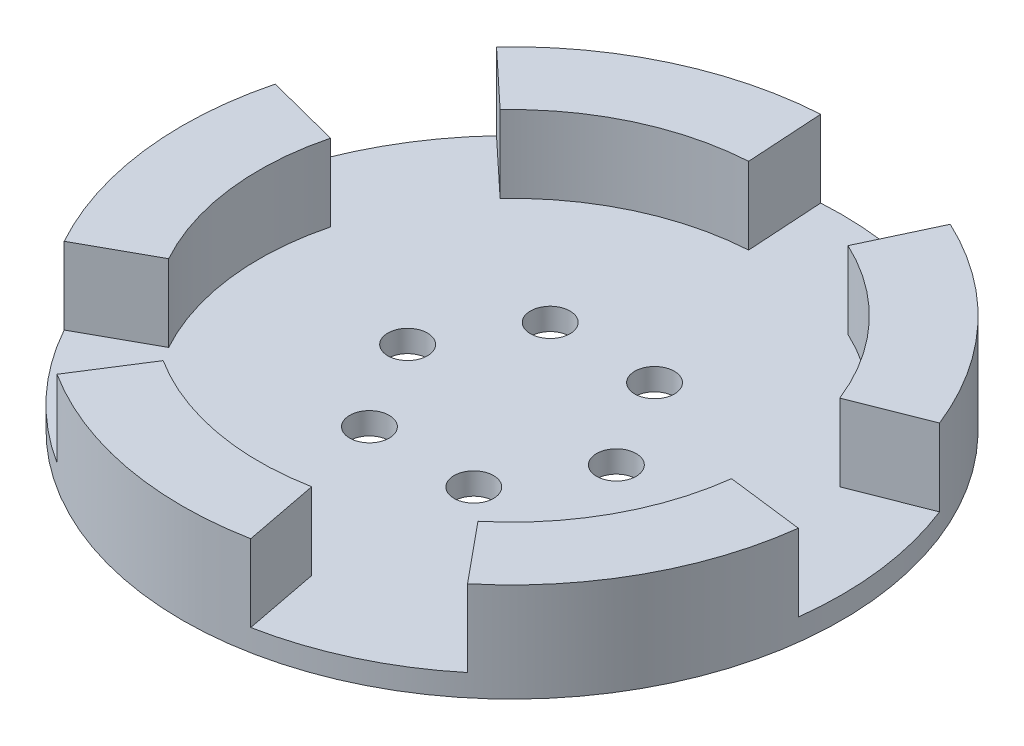
SolidWorks part; units mm, degrees
ref_plane "Front Plane" through (0, 0, 0) normal (0, 0, 1) x (1, 0, 0)
ref_plane "Top Plane" through (0, 0, 0) normal (0, 1, 0) x (1, 0, 0)
ref_plane "Right Plane" through (0, 0, 0) normal (1, 0, 0) x (0, 0, -1)
sketch "Sketch3" plane through (0, 0, 0) normal (0, 1, 0) x (1, 0, 0)
  circle A0 centre (0, 0) radius 30
  dimension "D2" = 60
extrude "Boss-Extrude3" add sketch "Sketch3" along normal blind 2
sketch "Sketch4" plane through (0, 2, 0) normal (0, 1, 0) x (1, 0, 0)
  line L0 (0, 0) -> (-16.7954, 15.7135) construction
  line L1 (0, 0) -> (9.7544, 20.8291) construction
  line L2 (0, 0) -> (21.3954, 8.4401) construction
  line L3 (0, 0) -> (22.8239, -2.8404) construction
  line L4 (0, 0) -> (14.6386, -17.7401) construction
  line L5 (0, 0) -> (4.3516, -22.5846) construction
  line L6 (0, 0) -> (-12.3483, -19.4041) construction
  line L7 (0, 0) -> (-20.1345, -11.1176) construction
  line L8 (0, 0) -> (-22.2702, 5.7477) construction
  line L9 (0, 0) -> (-1.4155, 22.9564) construction
  line L10 (-16.7954, 15.7135) -> (-1.4155, 22.9564) construction
  line L11 (-1.4155, 22.9564) -> (9.7544, 20.8291) construction
  line L12 (9.7544, 20.8291) -> (21.3954, 8.4401) construction
  line L13 (21.3954, 8.4401) -> (22.8239, -2.8404) construction
  line L14 (22.8239, -2.8404) -> (14.6386, -17.7401) construction
  line L15 (14.6386, -17.7401) -> (4.3516, -22.5846) construction
  line L16 (4.3516, -22.5846) -> (-12.3483, -19.4041) construction
  line L17 (-12.3483, -19.4041) -> (-20.1345, -11.1176) construction
  line L18 (-20.1345, -11.1176) -> (-22.2702, 5.7477) construction
  line L19 (-22.2702, 5.7477) -> (-16.7954, 15.7135) construction
  line L20 (14.6386, -17.7401) -> (19.0938, -23.1393)
  line L21 (22.8239, -2.8404) -> (29.7703, -3.7049)
  line L22 (21.3954, 8.4401) -> (27.9071, 11.0089)
  line L23 (9.7544, 20.8291) -> (12.7231, 27.1684)
  line L24 (-1.4155, 22.9564) -> (-1.8463, 29.9431)
  line L25 (-16.7954, 15.7135) -> (-21.907, 20.4959)
  line L26 (-22.2702, 5.7477) -> (-29.0482, 7.497)
  line L27 (-20.1345, -11.1176) -> (-26.2624, -14.5012)
  line L28 (-12.3483, -19.4041) -> (-16.1064, -25.3097)
  line L29 (4.3516, -22.5846) -> (5.676, -29.4582)
  circle A0 centre (0, 0) radius 23 construction
  arc A1 (-16.7954, 15.7135) -> (-1.4155, 22.9564) centre (0, 0) cw
  arc A2 (9.7544, 20.8291) -> (21.3954, 8.4401) centre (0, 0) cw
  arc A3 (22.8239, -2.8404) -> (14.6386, -17.7401) centre (0, 0) cw
  arc A4 (-12.3483, -19.4041) -> (4.3516, -22.5846) centre (0, 0) ccw
  arc A5 (-20.1345, -11.1176) -> (-22.2702, 5.7477) centre (0, 0) cw
  arc A6 (-1.8463, 29.9431) -> (-21.907, 20.4959) centre (0, 0) ccw
  arc A7 (-29.0482, 7.497) -> (-26.2624, -14.5012) centre (0, 0) ccw
  arc A8 (5.676, -29.4582) -> (-16.1064, -25.3097) centre (0, 0) cw
  arc A9 (12.7231, 27.1684) -> (27.9071, 11.0089) centre (0, 0) cw
  arc A10 (29.7703, -3.7049) -> (19.0938, -23.1393) centre (0, 0) cw
  circle A11 centre (0, 0) radius 30 construction
  dimension "D1" = 46
  dimension "D2" = 17
extrude "Boss-Extrude4" add sketch "Sketch4" along normal blind 7
sketch "Sketch5" plane through (0, 0, 0) normal (0, -1, 0) x (1, 0, 0)
  line L1 (4.75, -8.2272) -> (9.5, 0) construction
  line L2 (9.5, 0) -> (4.75, 8.2272) construction
  line L3 (4.75, 8.2272) -> (-4.75, 8.2272) construction
  line L4 (-4.75, 8.2272) -> (-9.5, 0) construction
  line L5 (-9.5, 0) -> (-4.75, -8.2272) construction
  line L6 (-4.75, -8.2272) -> (4.75, -8.2272) construction
  circle A0 centre (0, 0) radius 8.2272 construction
  circle A1 centre (-4.75, 8.2272) radius 1.8
  circle A2 centre (4.75, 8.2272) radius 1.8
  circle A3 centre (9.5, 0) radius 1.8
  circle A4 centre (4.75, -8.2272) radius 1.8
  circle A5 centre (-4.75, -8.2272) radius 1.8
  circle A6 centre (-9.5, 0) radius 1.8
  dimension "D1" = 3.6
  dimension "D2" = 19
extrude "Cut-Extrude1" cut sketch "Sketch5" against normal blind 10
